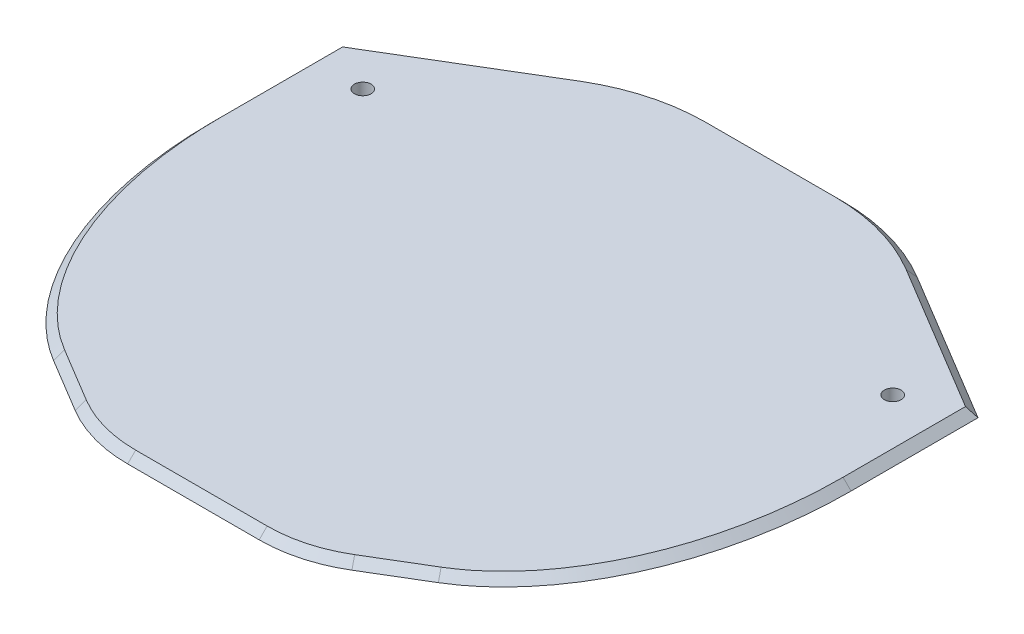
SolidWorks part; units mm, degrees
ref_plane "Front Plane" through (0, 0, 0) normal (0, 0, 1) x (1, 0, 0)
ref_plane "Top Plane" through (0, 0, 0) normal (0, 1, 0) x (1, 0, 0)
ref_plane "Right Plane" through (0, 0, 0) normal (1, 0, 0) x (0, 0, -1)
sketch "Sketch1" plane through (0, 30, 0) normal (0, 1, 0) x (1, 0, 0)
  line L80 (16.1508, 24.75) -> (-16.1508, 24.75)
  line L81 (74.75, -2.9725) -> (39.1745, 18.3728)
  line L82 (74.75, -31.7943) -> (74.75, -2.9725)
  line L83 (31.7311, -104.68) -> (46.2425, -95.9732)
  line L84 (-15.4886, -109.1789) -> (15.4886, -109.1789)
  line L85 (-46.2425, -95.9732) -> (-31.7311, -104.68)
  line L86 (-74.75, -2.9725) -> (-74.75, -31.7943)
  line L87 (-39.1745, 18.3728) -> (-74.75, -2.9725)
  line L88 (16.1508, 24.75) -> (-16.1508, 24.75)
  line L89 (74.75, -2.9725) -> (39.1745, 18.3728)
  line L90 (74.75, -31.7943) -> (74.75, -2.9725)
  line L91 (31.7311, -104.68) -> (46.2425, -95.9732)
  line L92 (-15.4886, -109.1789) -> (15.4886, -109.1789)
  line L93 (-46.2425, -95.9732) -> (-31.7311, -104.68)
  line L94 (-74.75, -2.9725) -> (-74.75, -31.7943)
  line L95 (-39.1745, 18.3728) -> (-74.75, -2.9725)
  arc A23 (39.1745, 18.3728) -> (16.1508, 24.75) centre (16.1508, -20) ccw
  arc A24 (-16.1508, 24.75) -> (-39.1745, 18.3728) centre (-16.1508, -20) ccw
  arc A25 (39.1745, 18.3728) -> (16.1508, 24.75) centre (16.1508, -20) ccw
  arc A26 (-16.1508, 24.75) -> (-39.1745, 18.3728) centre (-16.1508, -20) ccw
  spline S0 degree 3 poles (-4119.9389, 4210.7221) (-381.9705, 80.0854) (-33.9909, -158.1809) (51.2437, -92.4477) (52.3963, -91.4541) (54.6045, -89.3557) (55.6602, -88.2508) (57.1771, -86.5172) (57.6723, -85.9256) (58.6328, -84.7287) (59.0993, -84.1222) (61.367, -81.0518) (62.9767, -78.4761) (65.1411, -74.4663) (65.8205, -73.1052) (67.1004, -70.3368) (67.7019, -68.9275) (69.3883, -64.6475) (70.344, -61.7582) (71.9648, -55.9175) (72.6295, -52.9661) (73.6905, -47.006) (74.0866, -43.9973) (74.4843, -39.4423) (74.584, -37.915) (93.938, 407.7209) (-2691.385, 927.0941) (-5698.4505, 1452.4182) knots -4.288108 -4.288108 -4.288108 -4.288108 0.0625 0.0625 0.125 0.125 0.1875 0.1875 0.21875 0.21875 0.25 0.25 0.375 0.375 0.4375 0.4375 0.5 0.5 0.625 0.625 0.75 0.75 0.875 0.875 0.9375 0.9375 19.084959 19.084959 19.084959 19.084959 only from (46.2425, -95.9732) to (74.75, -31.7943)
  spline S1 degree 3 poles (-356.8152, -4110.572) (-1634.6956, 5520.3856) (-313.1628, -201.0547) (25.2573, -107.6747) (26.6151, -107.1972) (256.2571, -8.2692) (-770.5224, 2753.6884) (3193.2179, -5075.2167) knots -61.095461 -61.095461 -61.095461 -61.095461 0.5 0.5 0.75 0.75 44.335475 44.335475 44.335475 44.335475 only from (15.4886, -109.1789) to (31.7311, -104.68)
  spline S2 degree 3 poles (-2409.6787, -3344.2975) (1449.6347, 5571.6445) (-360.817, -14.3731) (-22.5805, -108.4161) (-21.1706, -108.7052) (226.6439, -142.025) (767.2032, 2754.6077) (138.144, -5997.9505) knots -61.095461 -61.095461 -61.095461 -61.095461 0.5 0.5 0.75 0.75 44.335475 44.335475 44.335475 44.335475 only from (-31.7311, -104.68) to (-15.4886, -109.1789)
  spline S3 degree 3 poles (5620.1907, 1729.3483) (1274.4797, 787.4237) (-101.5795, 272.3903) (-74.0926, -43.9424) (-73.6994, -46.9465) (-72.6403, -52.9155) (-71.9746, -55.8805) (-70.7502, -60.2954) (-70.3033, -61.7638) (-69.3381, -64.6607) (-68.8191, -66.0923) (-67.1473, -70.3342) (-65.8811, -73.092) (-63.717, -77.1064) (-62.9513, -78.4241) (-61.7286, -80.3663) (-61.308, -81.009) (-60.4438, -82.2771) (-60.001, -82.9015) (-57.7318, -85.9728) (-55.7416, -88.2709) (-52.4313, -91.4228) (-51.2715, -92.4253) (41.9685, -164.4009) (408.0843, 161.8763) (3633.0914, 4632.2187) knots -12.830757 -12.830757 -12.830757 -12.830757 0.125 0.125 0.25 0.25 0.375 0.375 0.4375 0.4375 0.5 0.5 0.625 0.625 0.6875 0.6875 0.71875 0.71875 0.75 0.75 0.875 0.875 0.9375 0.9375 5.653098 5.653098 5.653098 5.653098 only from (-74.75, -31.7943) to (-46.2425, -95.9732)
  spline S4 degree 3 poles (46.2425, -95.9732) (47.5679, -95.1779) (48.8295, -94.3096) (51.2437, -92.4477) (52.3963, -91.4541) (54.6045, -89.3557) (55.6602, -88.2508) (57.1771, -86.5172) (57.6723, -85.9256) (58.6328, -84.7287) (59.0993, -84.1222) (61.367, -81.0518) (62.9767, -78.4761) (65.1411, -74.4663) (65.8205, -73.1052) (67.1004, -70.3368) (67.7019, -68.9275) (69.3883, -64.6475) (70.344, -61.7582) (71.9648, -55.9175) (72.6295, -52.9661) (73.6905, -47.006) (74.0866, -43.9973) (74.4843, -39.4423) (74.584, -37.915) (74.7168, -34.856) (74.75, -33.3256) (74.75, -31.7943) knots 0 0 0 0 0.0625 0.0625 0.125 0.125 0.1875 0.1875 0.21875 0.21875 0.25 0.25 0.375 0.375 0.4375 0.4375 0.5 0.5 0.625 0.625 0.75 0.75 0.875 0.875 0.9375 0.9375 1 1 1 1
  spline S5 degree 3 poles (15.4886, -109.1789) (18.3524, -109.1789) (21.1533, -108.8071) (25.2573, -107.6747) (26.6151, -107.1972) (29.2344, -106.0688) (30.5028, -105.417) (31.7311, -104.68) knots 0 0 0 0 0.5 0.5 0.75 0.75 1 1 1 1
  spline S6 degree 3 poles (-31.7311, -104.68) (-29.2754, -106.1534) (-26.6823, -107.2757) (-22.5805, -108.4161) (-21.1706, -108.7052) (-18.344, -109.0853) (-16.921, -109.1789) (-15.4886, -109.1789) knots 0 0 0 0 0.5 0.5 0.75 0.75 1 1 1 1
  spline S7 degree 3 poles (-74.75, -31.7943) (-74.75, -34.855) (-74.618, -37.8966) (-74.0926, -43.9424) (-73.6994, -46.9465) (-72.6403, -52.9155) (-71.9746, -55.8805) (-70.7502, -60.2954) (-70.3033, -61.7638) (-69.3381, -64.6607) (-68.8191, -66.0923) (-67.1473, -70.3342) (-65.8811, -73.092) (-63.717, -77.1064) (-62.9513, -78.4241) (-61.7286, -80.3663) (-61.308, -81.009) (-60.4438, -82.2771) (-60.001, -82.9015) (-57.7318, -85.9728) (-55.7416, -88.2709) (-52.4313, -91.4228) (-51.2715, -92.4253) (-48.8323, -94.3083) (-47.5645, -95.18) (-46.2425, -95.9732) knots 0 0 0 0 0.125 0.125 0.25 0.25 0.375 0.375 0.4375 0.4375 0.5 0.5 0.625 0.625 0.6875 0.6875 0.71875 0.71875 0.75 0.75 0.875 0.875 0.9375 0.9375 1 1 1 1
  dimension "D1" = 0.25
extrude "Boss-Extrude1" add sketch "Sketch1" against normal blind 2.25 contours L94 S7 L93 S6 L92 S5 L91 S4 L90 L89 A25 L88 A26 L95
sketch "Sketch3" plane through (0, 30, 0) normal (0, 1, 0) x (1, 0, 0)
  line L8 (16.1508, 30) -> (-16.1508, 30)
  line L9 (-41.8756, 22.8746) -> (-80, 0)
  line L10 (-80, 0) -> (-80, -31.7943)
  line L11 (-48.1902, -103.3423) -> (-34.658, -111.4616)
  line L12 (-16.4679, -116.5) -> (16.4679, -116.5)
  line L13 (34.658, -111.4616) -> (48.1902, -103.3423)
  line L14 (80, -31.7943) -> (80, 0)
  line L15 (80, 0) -> (41.8756, 22.8746)
  line L16 (16.1508, 30) -> (-16.1508, 30)
  line L17 (-41.8756, 22.8746) -> (-80, 0)
  line L18 (-80, 0) -> (-80, -31.7943)
  line L19 (-48.1902, -103.3423) -> (-34.658, -111.4616)
  line L20 (-16.4679, -116.5) -> (16.4679, -116.5)
  line L21 (34.658, -111.4616) -> (48.1902, -103.3423)
  line L22 (80, -31.7943) -> (80, 0)
  line L23 (80, 0) -> (41.8756, 22.8746)
  arc A2 (-16.1508, 30) -> (-41.8756, 22.8746) centre (-16.1508, -20) ccw
  arc A3 (41.8756, 22.8746) -> (16.1508, 30) centre (16.1508, -20) ccw
  arc A4 (-16.1508, 30) -> (-41.8756, 22.8746) centre (-16.1508, -20) ccw
  arc A5 (41.8756, 22.8746) -> (16.1508, 30) centre (16.1508, -20) ccw
  ellipse E4 centre (-30, -31.7943) end of major axis (-30, 45.0171) minor radius 50 (-80, -31.7943) -> (-48.1902, -103.3423) ccw
  ellipse E5 centre (-6.675, -45.7893) end of major axis (-25.9087, -115.229) minor radius 50 (-34.658, -111.4616) -> (-16.4679, -116.5) ccw
  ellipse E6 centre (6.675, -45.7893) end of major axis (25.9087, -115.229) minor radius 50 (16.4679, -116.5) -> (34.658, -111.4616) ccw
  ellipse E7 centre (30, -31.7943) end of major axis (30, -108.6058) minor radius 50 (48.1902, -103.3423) -> (80, -31.7943) ccw
  ellipse E8 centre (-30, -31.7943) end of major axis (-30, 45.0171) minor radius 50 (-80, -31.7943) -> (-48.1902, -103.3423) ccw
  ellipse E9 centre (-6.675, -45.7893) end of major axis (-25.9087, -115.229) minor radius 50 (-34.658, -111.4616) -> (-16.4679, -116.5) ccw
  ellipse E10 centre (6.675, -45.7893) end of major axis (25.9087, -115.229) minor radius 50 (16.4679, -116.5) -> (34.658, -111.4616) ccw
  ellipse E11 centre (30, -31.7943) end of major axis (30, -108.6058) minor radius 50 (48.1902, -103.3423) -> (80, -31.7943) ccw
  dimension "D1" = 0
extrude "Boss-Extrude2" add sketch "Sketch3" along normal blind 2
chamfer "Chamfer1" distance 2 angle 45 14 edges at (60.9378, 32, -11.4373) (80, 32, 15.8972) (71.2887, 32, 75.1161) (41.4241, 32, 107.402) (25.9087, 32, 115.229) (0, 32, 116.5) (-25.9087, 32, 115.229) (-41.4241, 32, 107.402) (-71.2887, 32, 75.1161) (-80, 32, 15.8972) (-60.9378, 32, -11.4373) (-29.4975, 32, -28.1857) (0, 32, -30) (29.4975, 32, -28.1857)
sketch "Sketch2" plane through (0, 32, 0) normal (0, 1, 0) x (1, 0, 0)
  line L0 (66.3615, -3.1032) -> (62.3615, -5.4126) construction
  line L1 (70.3615, -5.4126) -> (66.3615, -3.1032) construction
  line L2 (70.3615, -10.0314) -> (70.3615, -5.4126) construction
  line L3 (66.3615, -12.3408) -> (70.3615, -10.0314) construction
  line L4 (62.3615, -10.0314) -> (66.3615, -12.3408) construction
  line L5 (62.3615, -5.4126) -> (62.3615, -10.0314) construction
  line L6 (66.3615, -3.1032) -> (62.3615, -5.4126) construction
  line L7 (70.3615, -5.4126) -> (66.3615, -3.1032) construction
  line L8 (70.3615, -10.0314) -> (70.3615, -5.4126) construction
  line L9 (66.3615, -12.3408) -> (70.3615, -10.0314) construction
  line L10 (62.3615, -10.0314) -> (66.3615, -12.3408) construction
  line L11 (62.3615, -5.4126) -> (62.3615, -10.0314) construction
  line L12 (0, -17.6006) -> (0, 17.6006) construction
  circle A0 centre (66.3615, -7.722) radius 2.1
  circle A1 centre (-66.3615, -7.722) radius 2.1
  point P7 (0, 0)
  point P9 (62.3615, -7.722)
  point P10 (0, 0)
  dimension "D1" = 4.2
extrude "Cut-Extrude3" cut sketch "Sketch2" against normal up to surface (4.25 mm away) up to face at (-5.3393, 27.75, 42.8445)
sketch "Sketch4" plane through (0, 0, 109.1789) normal (0, 0, 1) x (1, 0, 0)
  line L4 (15.4886, 30) -> (-15.4886, 30)
  line L5 (-15.4886, 30) -> (-15.4886, 27.75)
  line L6 (-15.4886, 27.75) -> (15.4886, 27.75)
  line L7 (15.4886, 27.75) -> (15.4886, 30)
  line L8 (15.4886, 30) -> (-15.4886, 30)
  line L9 (-15.4886, 30) -> (-15.4886, 27.75)
  line L10 (-15.4886, 27.75) -> (15.4886, 27.75)
  line L11 (15.4886, 27.75) -> (15.4886, 30)
  dimension "D1" = 0
extrude "Boss-Extrude3" add sketch "Sketch4" along normal up to surface (2.5 mm away)
